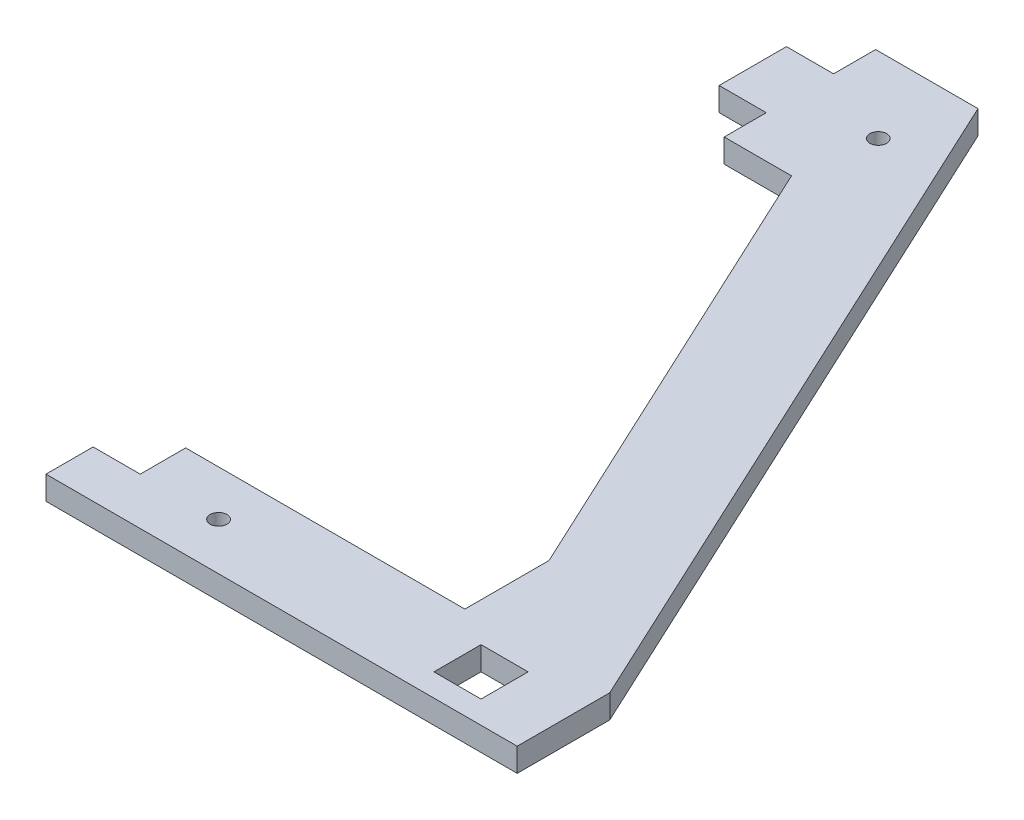
SolidWorks part; units mm, degrees
other "Markup1"
sketch "Sketch2" plane through (-140, 14, -235) normal (-0.4302, 0.8863, -0.1715) x (-0.3703, 0, 0.9289)
sketch "Sketch3" plane through (-140, 14, -232.5) normal (-0.4302, 0.8863, -0.1715) x (-0.3703, 0, 0.9289)
sketch "Sketch4" plane through (-140, 14, -232.5) normal (-0.4302, 0.8863, -0.1715) x (-0.3703, 0, 0.9289)
sketch "Sketch5" plane through (-140, 7, -232.5) normal (-0.4302, 0.8863, -0.1715) x (-0.3703, 0, 0.9289)
sketch "Sketch6" plane through (-140, 7, -232.5) normal (-0.4302, 0.8863, -0.1715) x (-0.3703, 0, 0.9289)
material "Maple"
ref_plane "Front Plane" through (0, 0, 0) normal (0, 0, 1) x (1, 0, 0)
ref_plane "Top Plane" through (0, 0, 0) normal (0, 1, 0) x (1, 0, 0)
ref_plane "Right Plane" through (0, 0, 0) normal (1, 0, 0) x (0, 0, -1)
sketch "Sketch1" plane through (0, 0, 0) normal (0, 1, 0) x (1, 0, 0)
  line L40 (0, 0) -> (0, 27.5)
  line L41 (-140, 0) -> (-140, 14)
  line L42 (-140, 14) -> (-126, 14)
  line L43 (-126, 14) -> (-126, 27.5)
  line L44 (-126, 27.5) -> (-43.0485, 27.5)
  line L45 (-126, 187.5) -> (-126, 200)
  line L46 (-126, 200) -> (-140, 200)
  line L47 (-140, 200) -> (-140, 220)
  line L48 (-140, 220) -> (-126, 220)
  line L49 (-126, 220) -> (-126, 232.5)
  line L50 (-43.0485, 52.5) -> (-43.0485, 27.5)
  line L52 (-140, 0) -> (0, 0)
  line L53 (-126, 187.5) -> (-106, 187.5)
  line L54 (-106, 187.5) -> (-43.0485, 52.5)
  line L55 (-95.5931, 232.5) -> (0, 27.5)
  line L56 (-126, 232.5) -> (-95.5931, 232.5)
  line L58 (-31.5, 20.75) -> (-17.5, 20.75)
  line L59 (-31.5, 20.75) -> (-31.5, 6.75)
  line L60 (-31.5, 6.75) -> (-17.5, 6.75)
  line L61 (-17.5, 20.75) -> (-17.5, 6.75)
  line L62 (-31.5, 20.75) -> (-17.5, 6.75) construction
  line L63 (-31.5, 6.75) -> (-17.5, 20.75) construction
  circle A0 centre (-102.73, 14) radius 2.5
  circle A1 centre (-102.73, 210) radius 2.5
  point P1 (-24.5, 13.75)
  point P25 (0, 0)
  point P29 (-140, 210)
  dimension "D9" = 115
  dimension "D15" = 23.27
  dimension "D16" = 5
  dimension "D1" = 14
  dimension "D2" = 140
  dimension "D3" = 27.5
  dimension "D4" = 20
  dimension "D5" = 25
  dimension "D7" = 232.5
  dimension "D8" = 20
  dimension "D10" = 135
  dimension "D11" = 14
  dimension "D12" = 17.5
  dimension "D13" = 6.75
  dimension "D14" = 14
extrude "Boss-Extrude1" add sketch "Sketch1" along normal blind 7
